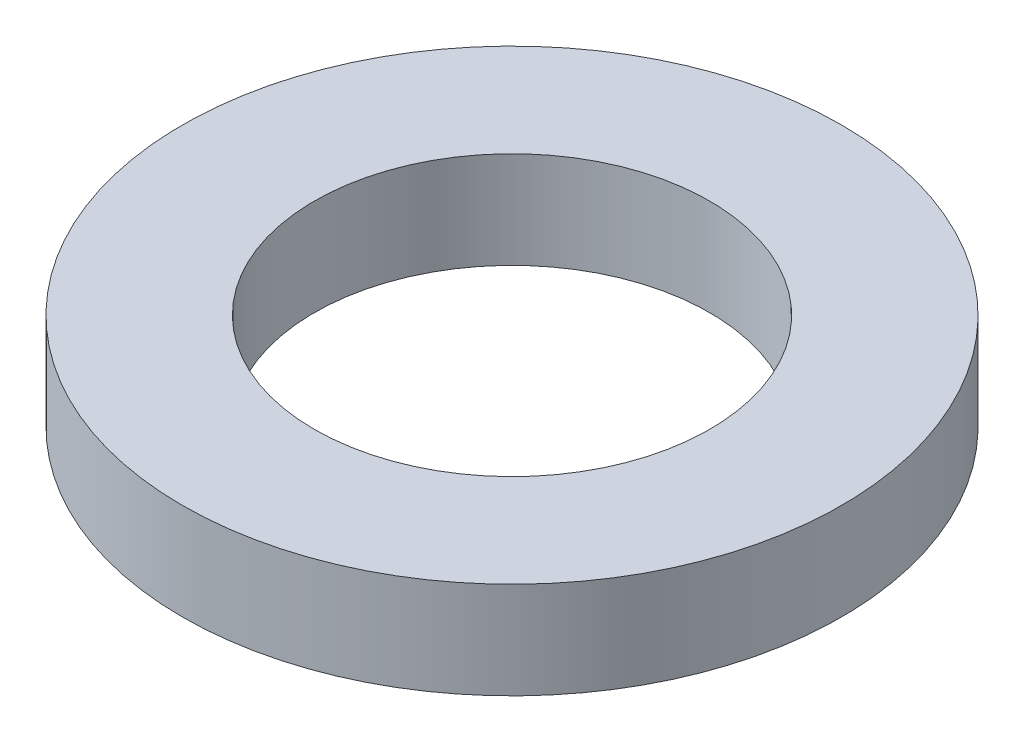
SolidWorks part; units mm, degrees
ref_plane "Front Plane" through (0, 0, 0) normal (0, 0, 1) x (1, 0, 0)
ref_plane "Top Plane" through (0, 0, 0) normal (0, 1, 0) x (1, 0, 0)
ref_plane "Right Plane" through (0, 0, 0) normal (1, 0, 0) x (0, 0, -1)
sketch "Sketch1" plane through (0, 0, 0) normal (0, 1, 0) x (1, 0, 0)
  circle A0 centre (0, 0) radius 37.5
  dimension "FLANGE_OD" = 75
extrude "Boss-Extrude1" add sketch "Sketch1" along normal blind 11
sketch "Sketch2" plane through (0, 0, 0) normal (0, 1, 0) x (1, 0, 0)
  circle A0 centre (0, 0) radius 22.5
  dimension "BORE_D" = 45
extrude "Cut-Extrude1" cut sketch "Sketch2" along normal through all
sketch "Sketch3" plane through (0, 11, 0) normal (0, 1, 0) x (1, 0, 0)
  circle A0 centre (0, 0) radius 14.2406 construction
  circle A1 centre (-14.2406, 0) radius 1.659
  dimension "BOLT_D" = 3.318
  dimension "BOLT_PCD" = 28.4812
extrude "Cut-Extrude2" cut sketch "Sketch3" against normal blind 8.2328 rebuild error yes
pattern_circular "CirPattern1" count 5 over 360 rebuild error yes
